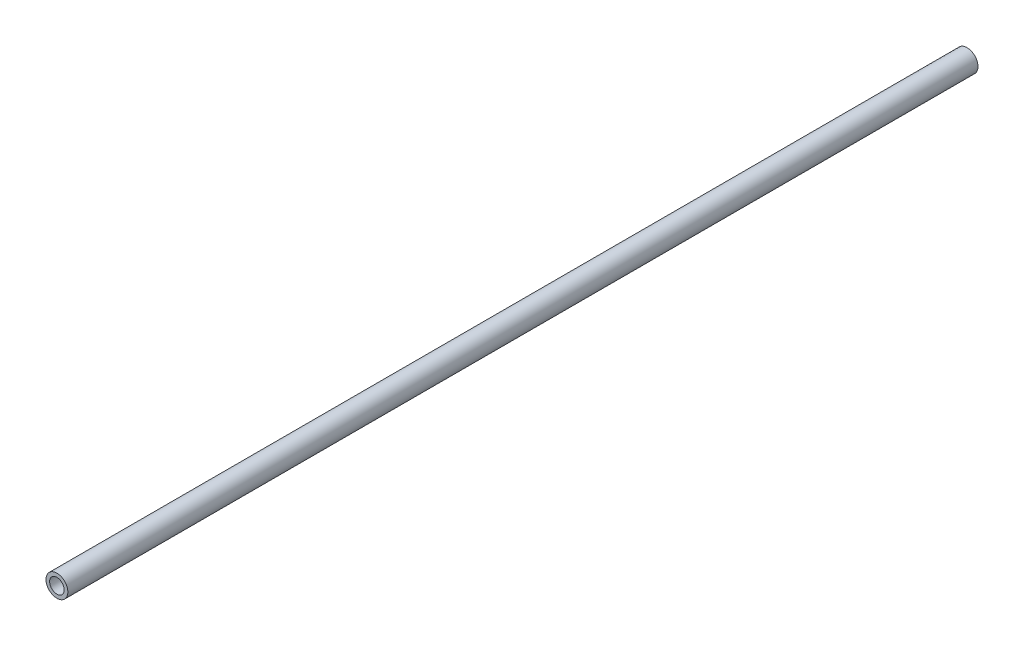
SolidWorks part; units mm, degrees
material "Carbon Fiber Rod"
ref_plane "Front Plane" through (0, 0, 0) normal (0, 0, 1) x (1, 0, 0)
ref_plane "Top Plane" through (0, 0, 0) normal (0, 1, 0) x (1, 0, 0)
ref_plane "Right Plane" through (0, 0, 0) normal (1, 0, 0) x (0, 0, -1)
sketch "Sketch1" plane through (0, 0, 0) normal (0, 0, 1) x (1, 0, 0)
  circle A0 centre (0, 0) radius 3
  circle A1 centre (0, 0) radius 2
  dimension "D1" = 6
  dimension "D2" = 4
extrude "Boss-Extrude1" add sketch "Sketch1" along normal blind 250
